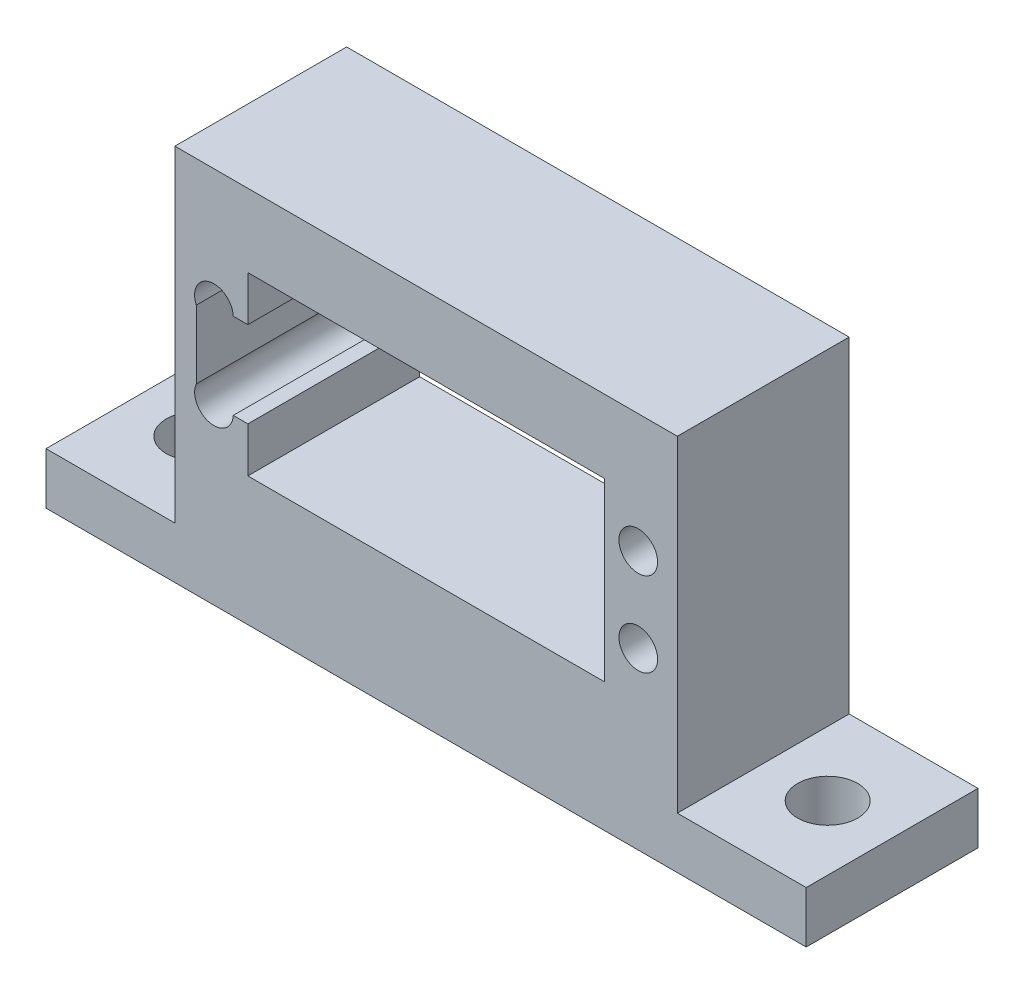
SolidWorks part; units mm, degrees
ref_plane "Front Plane" through (0, 0, 0) normal (0, 0, 1) x (1, 0, 0)
ref_plane "Top Plane" through (0, 0, 0) normal (0, 1, 0) x (1, 0, 0)
ref_plane "Right Plane" through (0, 0, 0) normal (1, 0, 0) x (0, 0, -1)
sketch "Sketch1" plane through (0, 0, 0) normal (0, 0, 1) x (1, 0, 0)
  line L0 (-44.25, 0) -> (44.25, 0)
  line L1 (44.25, 0) -> (44.25, 6)
  line L2 (44.25, 6) -> (29.25, 6)
  line L3 (29.25, 6) -> (29.25, 44)
  line L4 (29.25, 44) -> (-29.25, 44)
  line L5 (0, 0) -> (0, 132.122) construction
  line L6 (-20.75, 35.5) -> (20.75, 35.5)
  line L7 (20.75, 35.5) -> (20.75, 15)
  line L8 (20.75, 15) -> (-20.75, 15)
  line L10 (-29.25, 6) -> (-29.25, 44)
  line L11 (-44.25, 6) -> (-29.25, 6)
  line L12 (-44.25, 0) -> (-44.25, 6)
  line L13 (-20.75, 30.25) -> (-22.4522, 30.25)
  line L14 (-26.75, 29.2226) -> (-26.75, 21.2774)
  line L15 (-22.4522, 20.25) -> (-20.75, 20.25)
  line L16 (-20.75, 35.5) -> (-20.75, 30.25)
  line L18 (-20.75, 20.25) -> (-20.75, 15)
  line L20 (20.75, 25.25) -> (36.6589, 25.25) construction
  circle A0 centre (24.7, 30.15) radius 2.25
  circle A1 centre (24.7, 20.35) radius 2.25
  arc A2 (-26.75, 21.2774) -> (-22.4522, 20.25) centre (-24.7, 20.35) ccw
  arc A3 (-26.75, 29.2226) -> (-22.4522, 30.25) centre (-24.7, 30.15) cw
  point P15 (-26.75, 25.25)
  point P18 (0, 15)
  point P19 (0, 35.5)
  point P20 (0, 44)
  dimension "D11" = 4.5
  dimension "D1" = 41.5
  dimension "D2" = 20.5
  dimension "D3" = 15
  dimension "D4" = 8.5
  dimension "D5" = 15
  dimension "D6" = 8.5
  dimension "D7" = 6
  dimension "D8" = 10
  dimension "D9" = 6
  dimension "D10" = 49.4
  dimension "D12" = 4.9
  dimension "D13" = 5
extrude "Boss-Extrude1" add sketch "Sketch1" along normal blind 20
sketch "Sketch2" plane through (0, 6, 0) normal (0, 1, 0) x (1, 0, 0)
  line L0 (44.25, -10) -> (-44.25, -10) construction
  line L1 (44.25, -20) -> (44.25, 0) construction
  line L2 (-44.25, -20) -> (-44.25, 0) construction
  line L3 (36.75, 0) -> (36.75, -20) construction
  line L4 (44.25, 0) -> (29.25, 0) construction
  line L5 (44.25, -20) -> (29.25, -20) construction
  line L6 (0, 0) -> (0, -20) construction
  line L7 (29.25, 0) -> (-29.25, 0) construction
  line L8 (29.25, -20) -> (-29.25, -20) construction
  circle A0 centre (36.75, -10) radius 3.5
  circle A1 centre (-36.75, -10) radius 3.5
  dimension "D1" = 7
extrude "Cut-Extrude1" cut sketch "Sketch2" against normal through all
